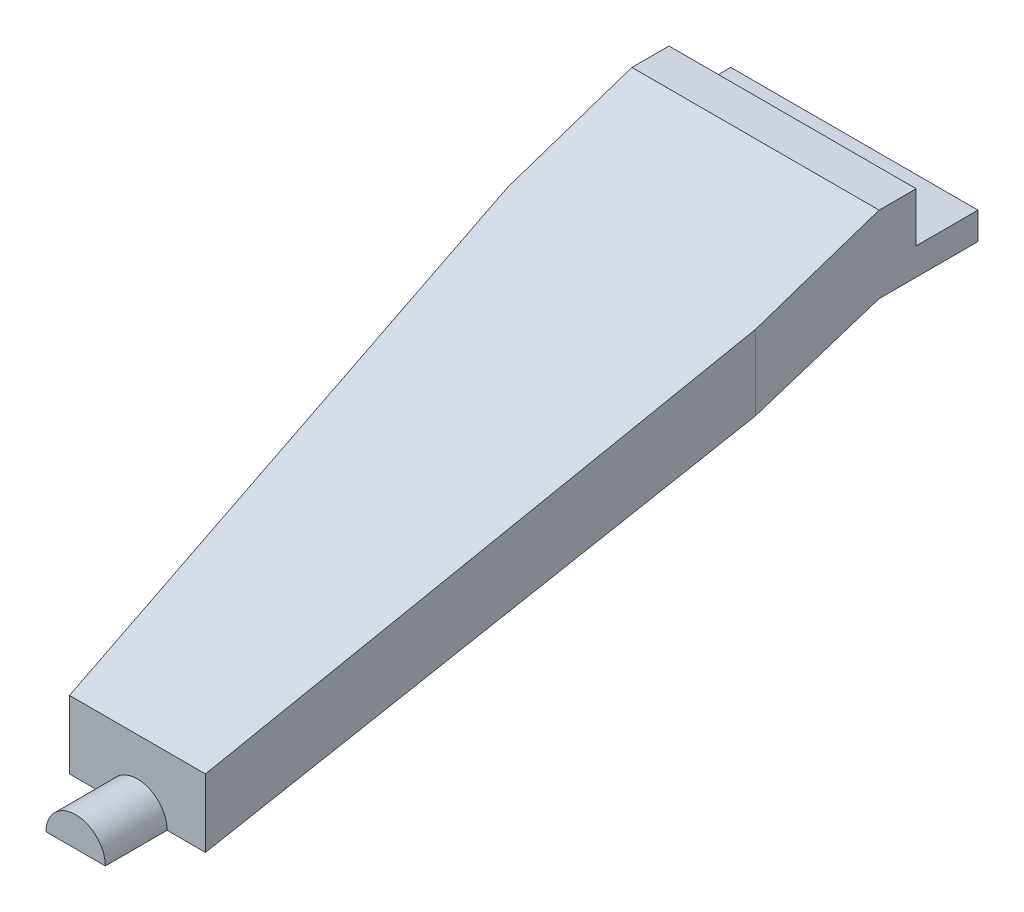
SolidWorks part; units mm, degrees
ref_plane "前视基准面" through (0, 0, 0) normal (0, 0, 1) x (1, 0, 0)
ref_plane "上视基准面" through (0, 0, 0) normal (0, 1, 0) x (1, 0, 0)
ref_plane "右视基准面" through (0, 0, 0) normal (1, 0, 0) x (0, 0, -1)
other "Configuration Table"
sketch "草图1" plane through (0, 0, 0) normal (0, 1, 0) x (1, 0, 0)
  line L1 (0, 0) -> (20, 0)
  line L2 (0, 0) -> (0, -5)
  line L3 (0, -5) -> (20, -5)
  line L4 (20, 0) -> (20, -5)
  circle A0 centre (4, -2.5) radius 0.8
  circle A1 centre (16, -2.5) radius 0.8
  dimension "D3" = 2.5
  dimension "D6" = 1.6
  dimension "D1" = 5
  dimension "D2" = 20
  dimension "D4" = 4
  dimension "D5" = 4
extrude "凸台-拉伸1" add sketch "草图1" along normal blind 2.2 contours L2 L3 L4 L1 | A0 | A1
sketch "草图2" plane through (0, 0, 5) normal (0, 0, 1) x (1, 0, 0)
  line L1 (0, 0) -> (20, 0)
  line L2 (0, 0) -> (0, 6.2)
  line L3 (0, 6.2) -> (20, 6.2)
  line L4 (20, 0) -> (20, 6.2)
  dimension "D1" = 6.2
  dimension "D2" = 20
extrude "凸台-拉伸2" add sketch "草图2" along normal blind 3 contours L3 L4 L1 L2
sketch "草图3" plane through (20, 0, 0) normal (1, 0, 0) x (0, 0, -1)
  line L0 (-8, 6.2) -> (-58, -10.55)
  line L1 (-58, -10.55) -> (-58, -16.05)
  line L2 (-58, -16.05) -> (-8, 0)
  line L3 (-8, 0) -> (-8, 6.2) construction
  line L5 (-58, -10.55) -> (-63, -10.55)
  line L6 (-58, -10.55) -> (-58, -16.05)
  line L7 (-58, -16.05) -> (-63, -16.05)
  line L8 (-63, -10.55) -> (-63, -16.05)
  line M7 (-8, 6.2) -> (-8, 0)
  dimension "D1" = 16.05
  dimension "D2" = 50
  dimension "D3" = 5.5
  dimension "D4" = 5
extrude "凸台-拉伸3" add sketch "草图3" against normal through all contours L1 L2 L0 M7 | L5 L8 L7 L1 region at (20, -4.9365, 32.5014) region at (20, -13.3, 60.5)
sketch "草图4" plane through (0, 6.2, 0) normal (0, 1, 0) x (1, 0, 0)
  line L0 (0, -8) -> (0, -58) construction
  line L1 (20, -8) -> (0, -8)
  line L2 (20, -8) -> (20, -18)
  line L3 (20, -18) -> (0, -18)
  line L4 (0, -8) -> (0, -18)
  line L5 (0, -63) -> (20, -63) construction
  line L6 (15.5, -63) -> (4.5, -63)
  line L7 (15.5, -63) -> (15.5, -58)
  line L8 (15.5, -58) -> (4.5, -58)
  line L9 (4.5, -63) -> (4.5, -58)
  line L10 (0, -58) -> (20, -58) construction
  line L11 (15.5, -58) -> (20, -58)
  line L12 (4.5, -58) -> (0, -58)
  line L13 (0, -58) -> (0, -63) construction
  line L14 (15.5, -58) -> (20, -18)
  line L15 (4.5, -58) -> (0, -18)
  line L16 (0, -18) -> (0, -63)
  line L17 (0, -63) -> (4.5, -63)
  line L18 (15.5, -63) -> (20, -63)
  line L19 (20, -63) -> (20, -18)
  dimension "D1" = 10
  dimension "D2" = 11
extrude "切除-拉伸1" cut sketch "草图4" against normal through all contours L15 L16 L12 | L11 L19 L14 | L18 L19 L11 L7 | L16 L17 L9 L12 region at (18.5, 6.2, 44.6667) region at (1.5, 6.2, 44.6667) region at (17.75, 6.2, 60.5) region at (2.25, 6.2, 60.5)
sketch "草图5" plane through (0, 0, 63) normal (0, 0, 1) x (1, 0, 0)
  line L0 (4.5, -16.05) -> (15.5, -16.05) construction
  line L2 (4.5, -10.55) -> (15.5, -10.55)
  line L3 (4.5, -10.55) -> (4.5, -16.05)
  line L4 (4.5, -16.05) -> (15.5, -16.05)
  line L5 (15.5, -10.55) -> (15.5, -16.05)
  circle A0 centre (10, -16.05) radius 2.4
  line M1 (4.5, -16.05) -> (15.5, -16.05)
  line M2 (15.5, -16.05) -> (15.5, -10.55)
  line M3 (15.5, -10.55) -> (4.5, -10.55)
  line M4 (4.5, -10.55) -> (4.5, -16.05)
  dimension "D1" = 4.8
extrude "切除-拉伸2" cut sketch "草图5" against normal blind 5 contours A0 M1 M2 M3 M4 region at (10, -12.9955, 63)
